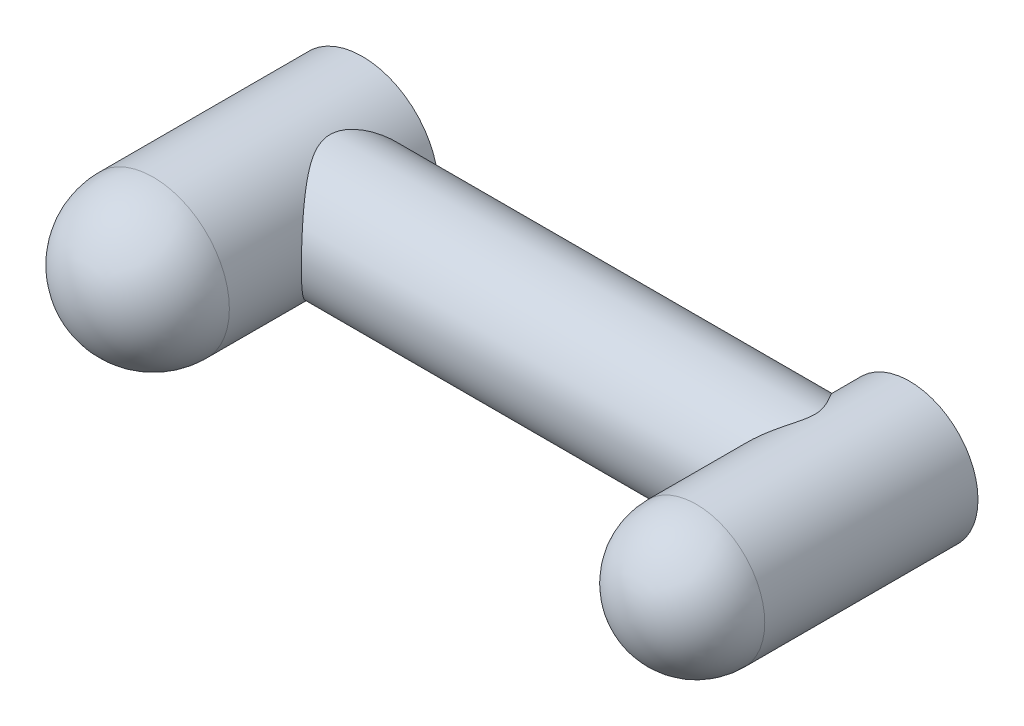
SolidWorks part; units mm, degrees
material "2014-T4"
ref_plane "Front Plane" through (0, 0, 0) normal (0, 0, 1) x (1, 0, 0)
ref_plane "Top Plane" through (0, 0, 0) normal (0, 1, 0) x (1, 0, 0)
ref_plane "Right Plane" through (0, 0, 0) normal (1, 0, 0) x (0, 0, -1)
sketch "Sketch1" plane through (0, 0, 0) normal (0, 0, 1) x (1, 0, 0)
  circle A0 centre (0, 0) radius 60
  dimension "D1" = 120
extrude "Boss-Extrude1" add sketch "Sketch1" along normal blind 225
fillet "Fillet1" radius 60 1 edges at (60, 0, 225)
sketch "Sketch2" plane through (0, 0, 0) normal (1, 0, 0) x (0, 0, -1)
  line L0 (0, -60) -> (0, 60) construction
  circle A0 centre (-57.15, 0) radius 51
  dimension "D2" = 102
  dimension "D1" = 57.15
extrude "Boss-Extrude2" add sketch "Sketch2" along normal blind 431.8
ref_axis "Axis1" through (431.8, 0, 57.15) along (-1, 0, 0)
ref_plane "Plane1" through (0, 0, 57.15) normal (0, 0, 1) x (1, 0, 0)
sketch "Sketch3" plane through (0, 0, 57.15) normal (0, 0, 1) x (1, 0, 0)
  line L0 (431.8, -51) -> (431.8, 51) construction
  line L1 (431.8, -51) -> (431.8, 51)
  circle A0 centre (431.8, 0) radius 53.975
  dimension "D1" = 107.95
extrude "Boss-Extrude3" add sketch "Sketch3" along normal blind 165.1 and the other way blind 57.15 contours A0 region at (379.3516, 0, 57.15)
fillet "Fillet2" radius 53.975 1 edges at (485.775, 0, 222.25)
shell "Shell1" thickness 5 removed face at (60, 0, 0) removed face at (485.775, 0, 0)
